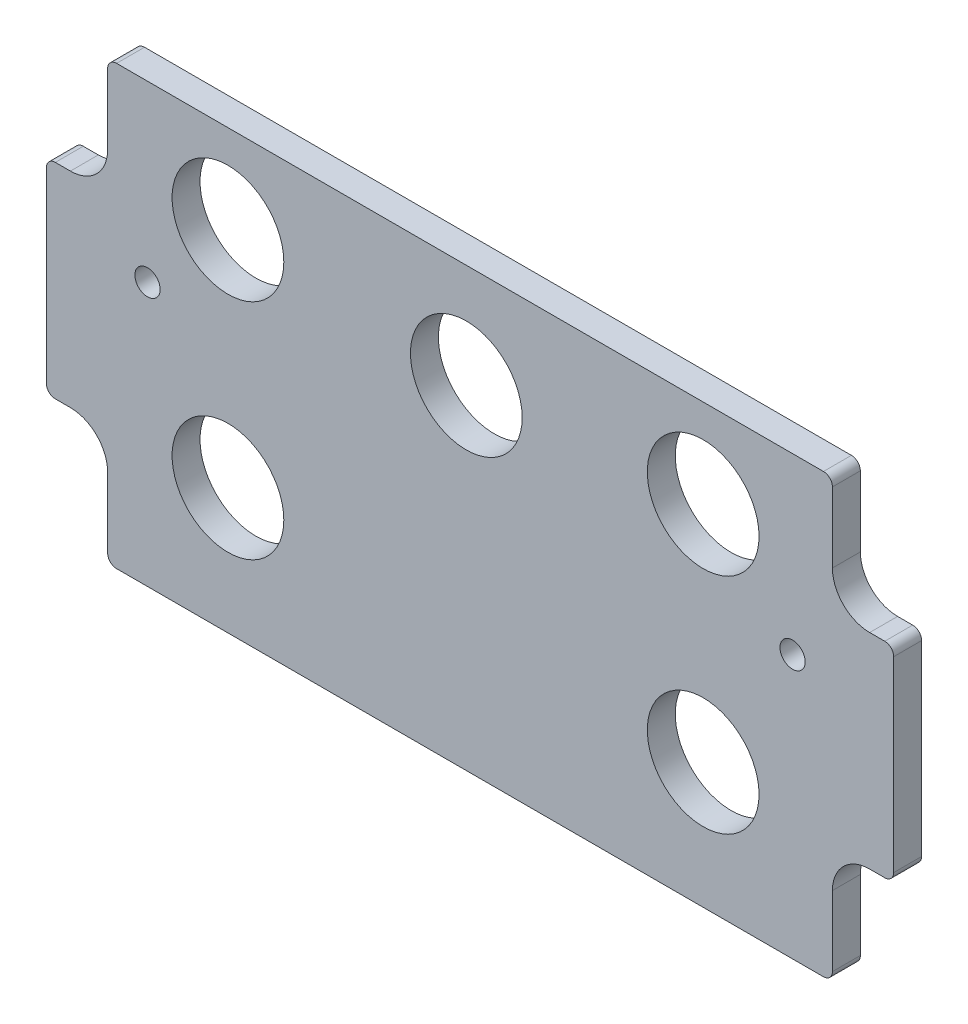
SolidWorks part; units mm, degrees
ref_plane "Front Plane" through (0, 0, 0) normal (0, 0, 1) x (1, 0, 0)
ref_plane "Top Plane" through (0, 0, 0) normal (0, 1, 0) x (1, 0, 0)
ref_plane "Right Plane" through (0, 0, 0) normal (1, 0, 0) x (0, 0, -1)
sketch "Sketch1" plane through (0, 0, 0) normal (0, 0, 1) x (1, 0, 0)
  line L12 (134.8105, 61.9125) -> (134.8105, 73.8822)
  line L13 (133.2865, 75.4062) -> (12.7635, 75.4062)
  line L14 (11.2395, 73.8822) -> (11.2395, 61.9125)
  line L15 (4.8895, 55.5625) -> (2.3178, 55.5625)
  line L16 (0.7938, 54.0385) -> (0.7938, 22.1615)
  line L17 (2.3178, 20.6375) -> (4.8895, 20.6375)
  line L18 (11.2395, 14.2875) -> (11.2395, 2.3178)
  line L19 (12.7635, 0.7938) -> (133.2865, 0.7937)
  line L20 (134.8105, 2.3177) -> (134.8105, 14.2875)
  line L21 (141.1605, 20.6375) -> (143.7323, 20.6375)
  line L22 (145.2563, 22.1615) -> (145.2563, 54.0385)
  line L23 (143.7323, 55.5625) -> (141.1605, 55.5625)
  line L24 (134.8105, 61.9125) -> (134.8105, 73.8822)
  line L25 (133.2865, 75.4062) -> (12.7635, 75.4062)
  line L26 (11.2395, 73.8822) -> (11.2395, 61.9125)
  line L27 (4.8895, 55.5625) -> (2.3178, 55.5625)
  line L28 (0.7938, 54.0385) -> (0.7938, 22.1615)
  line L29 (2.3178, 20.6375) -> (4.8895, 20.6375)
  line L30 (11.2395, 14.2875) -> (11.2395, 2.3178)
  line L31 (12.7635, 0.7938) -> (133.2865, 0.7937)
  line L32 (134.8105, 2.3177) -> (134.8105, 14.2875)
  line L33 (141.1605, 20.6375) -> (143.7323, 20.6375)
  line L34 (145.2563, 22.1615) -> (145.2563, 54.0385)
  line L35 (143.7323, 55.5625) -> (141.1605, 55.5625)
  arc A12 (134.8105, 61.9125) -> (141.1605, 55.5625) centre (141.1605, 61.9125) ccw
  arc A13 (134.8105, 73.8822) -> (133.2865, 75.4062) centre (133.2865, 73.8822) ccw
  arc A14 (12.7635, 75.4062) -> (11.2395, 73.8822) centre (12.7635, 73.8822) ccw
  arc A15 (4.8895, 55.5625) -> (11.2395, 61.9125) centre (4.8895, 61.9125) ccw
  arc A16 (2.3178, 55.5625) -> (0.7938, 54.0385) centre (2.3178, 54.0385) ccw
  arc A17 (0.7938, 22.1615) -> (2.3178, 20.6375) centre (2.3178, 22.1615) ccw
  arc A18 (11.2395, 14.2875) -> (4.8895, 20.6375) centre (4.8895, 14.2875) ccw
  arc A19 (11.2395, 2.3178) -> (12.7635, 0.7938) centre (12.7635, 2.3178) ccw
  arc A20 (133.2865, 0.7937) -> (134.8105, 2.3177) centre (133.2865, 2.3177) ccw
  arc A21 (141.1605, 20.6375) -> (134.8105, 14.2875) centre (141.1605, 14.2875) ccw
  arc A22 (143.7323, 20.6375) -> (145.2563, 22.1615) centre (143.7323, 22.1615) ccw
  arc A23 (145.2563, 54.0385) -> (143.7323, 55.5625) centre (143.7323, 54.0385) ccw
  arc A24 (134.8105, 61.9125) -> (141.1605, 55.5625) centre (141.1605, 61.9125) ccw
  arc A25 (134.8105, 73.8822) -> (133.2865, 75.4062) centre (133.2865, 73.8822) ccw
  arc A26 (12.7635, 75.4062) -> (11.2395, 73.8822) centre (12.7635, 73.8822) ccw
  arc A27 (4.8895, 55.5625) -> (11.2395, 61.9125) centre (4.8895, 61.9125) ccw
  arc A28 (2.3178, 55.5625) -> (0.7938, 54.0385) centre (2.3178, 54.0385) ccw
  arc A29 (0.7938, 22.1615) -> (2.3178, 20.6375) centre (2.3178, 22.1615) ccw
  arc A30 (11.2395, 14.2875) -> (4.8895, 20.6375) centre (4.8895, 14.2875) ccw
  arc A31 (11.2395, 2.3178) -> (12.7635, 0.7938) centre (12.7635, 2.3178) ccw
  arc A32 (133.2865, 0.7937) -> (134.8105, 2.3177) centre (133.2865, 2.3177) ccw
  arc A33 (141.1605, 20.6375) -> (134.8105, 14.2875) centre (141.1605, 14.2875) ccw
  arc A34 (143.7323, 20.6375) -> (145.2563, 22.1615) centre (143.7323, 22.1615) ccw
  arc A35 (145.2563, 54.0385) -> (143.7323, 55.5625) centre (143.7323, 54.0385) ccw
  dimension "D1" = 0
extrude "Boss-Extrude1" add sketch "Sketch1" along normal blind 4.7625
hole_wizard "3/4 (0.75) Diameter Hole1" positions "Sketch3" profile "Sketch2" hole size "3/4" standard "ANSI Inch" end condition through all
sketch "Sketch3" plane through (0, 0, 4.7625) normal (0, 0, 1) x (1, 0, 0)
  point P0 (31.75, 60.325)
  point P4 (72.39, 57.658)
  point P7 (112.776, 60.325)
  point P10 (112.776, 22.225)
  point P13 (31.75, 22.225)
  point P19 (0, 0)
sketch "Sketch2" plane through (31.75, 60.325, 4.7625) normal (1, 0, 0) x (0, -1, 0)
  line L0 (0, 0) -> (0, 4.7625)
  line L1 (0, 4.7625) -> (9.525, 4.7625)
  line L2 (9.525, 4.7625) -> (9.525, 0)
  line L5 (9.525, 0) -> (0, 0)
  line L11 (0, -6.35) -> (0, 107.95) construction
  dimension "Thru Hole Dia." = 19.05
  dimension "Thru Hole Depth" = 4.7625
hole_wizard "#6 Clearance Hole1" positions "Sketch5" profile "Sketch4" hole size "#6" standard "ANSI Inch" end condition through all
sketch "Sketch5" plane through (0, 0, 4.7625) normal (0, 0, 1) x (1, 0, 0)
  point P0 (18.034, 45.72)
  point P3 (128.016, 45.72)
sketch "Sketch4" plane through (18.034, 45.72, 4.7625) normal (1, 0, 0) x (0, -1, 0)
  line L0 (0, 0) -> (0, 4.7625)
  line L1 (0, 4.7625) -> (2.1526, 4.7625)
  line L2 (2.1526, 4.7625) -> (2.1526, 0)
  line L5 (2.1526, 0) -> (0, 0)
  line L11 (0, -6.35) -> (0, 107.95) construction
  dimension "Thru Hole Dia." = 4.3053
  dimension "Thru Hole Depth" = 4.7625
